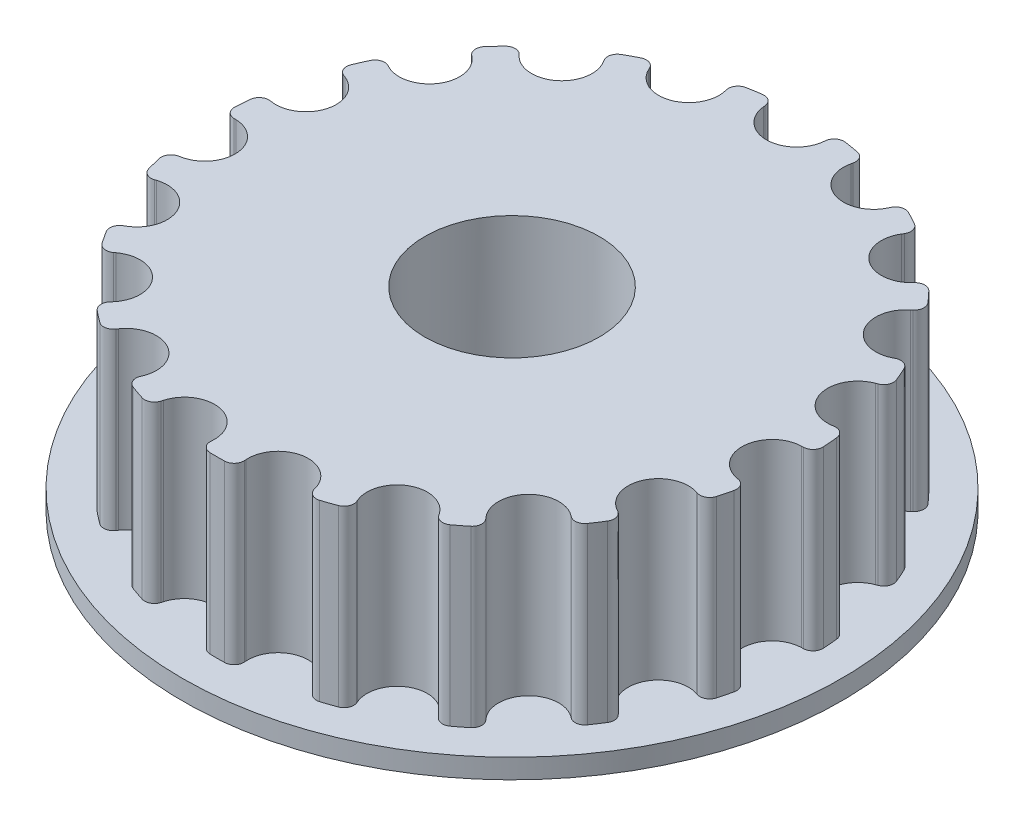
SolidWorks part; units mm, degrees
ref_plane "Front Plane" through (0, 0, 0) normal (0, 0, 1) x (1, 0, 0)
ref_plane "Top Plane" through (0, 0, 0) normal (0, 1, 0) x (1, 0, 0)
ref_plane "Right Plane" through (0, 0, 0) normal (1, 0, 0) x (0, 0, -1)
sketch "Эскиз1" plane through (0, 0, 0) normal (0, 1, 0) x (1, 0, 0)
  circle A3 centre (0, 0) radius 17
  dimension "D1" = 34
extrude "Бобышка-Вытянуть1" add sketch "Эскиз1" along normal blind 4.01 contours A3
sketch "Эскиз2" plane through (0, 0, 0) normal (0, -1, 0) x (1, 0, 0)
  circle A0 centre (0, 0) radius 11.05
  dimension "D1" = 22.1
sketch "Эскиз3" plane through (0, 4.01, 0) normal (0, 1, 0) x (1, 0, 0)
  circle A22 centre (0, 0) radius 15.205
  dimension "D1" = 30.41
extrude "Бобышка-Вытянуть2" add sketch "Эскиз3" along normal blind 9 contours A22
sketch "Эскиз4" plane through (0, 13.01, 0) normal (0, 1, 0) x (1, 0, 0)
  circle A0 centre (0, 0) radius 4.5
  dimension "D1" = 9
extrude "Вырез-Вытянуть2" cut sketch "Эскиз4" against normal through all
sketch "Эскиз5" plane through (0, 13.01, 0) normal (0, 1, 0) x (1, 0, 0)
  line L0 (0, 0) -> (-2.2472, 21.0338)
  line L1 (0, 0) -> (2.2472, 21.0344)
  line L2 (-2.2472, 21.0338) -> (2.2472, 21.0344)
  circle A0 centre (0, 0) radius 13.125
  circle A1 centre (0, 14.685) radius 1.56
  circle A2 centre (0, 0) radius 15.205
  dimension "D1" = 26.25
  dimension "D2" = 30.41
  dimension "D3" = 3.12
extrude "Вырез-Вытянуть4" cut sketch "Эскиз5" against normal blind 9 contours A1 L2 | A1 L1 L2 | A1 L2 L0 region at (-1.5635, 13.01, -14.9739) region at (0, 13.01, -14.2813) region at (1.5635, 13.01, -14.9739)
fillet "Скругление2" radius 0.5 2 edges at (-1.6152, 8.51, -15.119) (1.6152, 8.51, -15.119)
pattern_circular "Круговой массив7" count 19 over 360 about axis through (0, 0, 0) along (0, 1, 0) of "Скругление2", "Вырез-Вытянуть4" reverse direction yes
extrude "Вырез-Вытянуть5" cut sketch "Эскиз2" against normal up to surface (4.01 mm away) rebuild error yes
sketch "Эскиз6" plane through (0, 0, 0) normal (0, -1, 0) x (1, 0, 0)
  circle A0 centre (0, 0) radius 17
extrude "Вырез-Вытянуть6" cut sketch "Эскиз6" against normal blind 3
sketch "Эскиз7" plane through (0, 3, 0) normal (0, -1, 0) x (1, 0, 0)
  circle A0 centre (0, 0) radius 11.15
extrude "Вырез-Вытянуть7" cut sketch "Эскиз7" against normal blind 3.6
